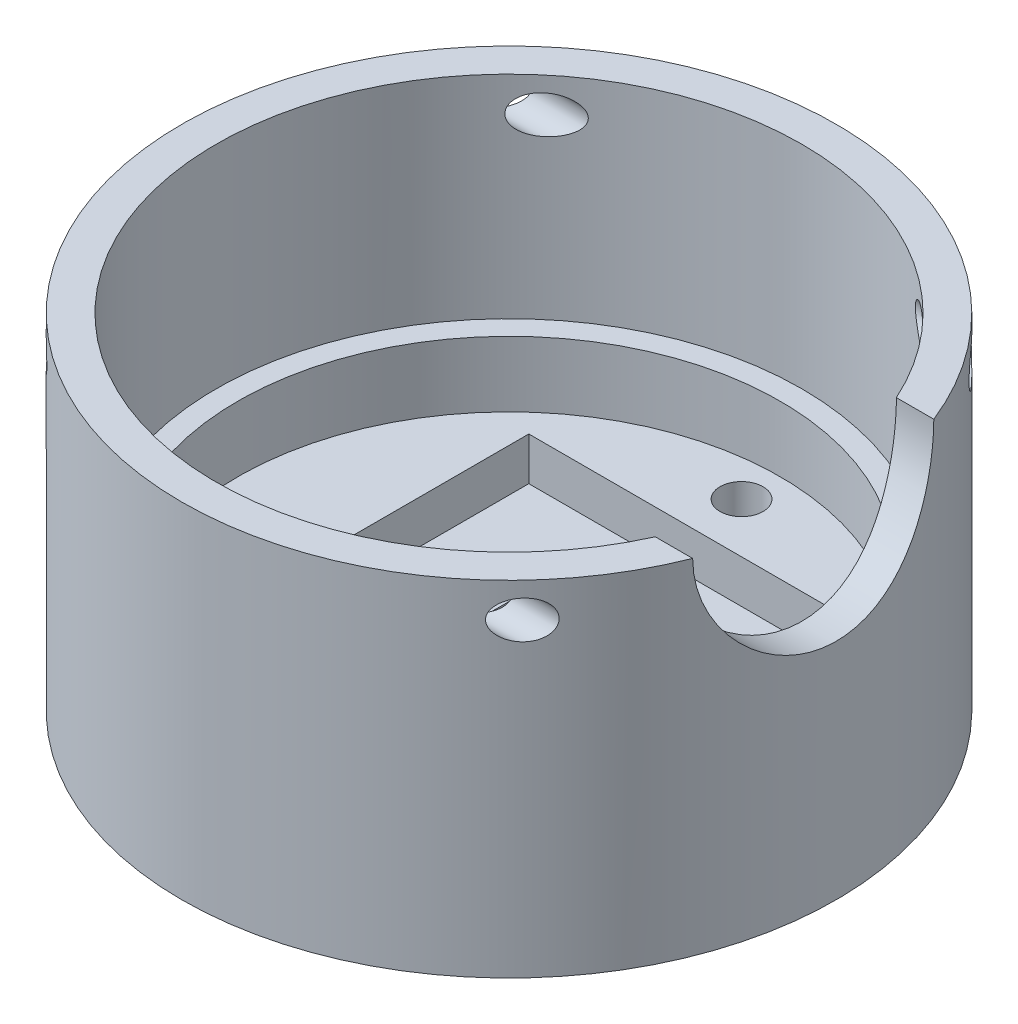
SolidWorks part; units mm, degrees
ref_plane "Front Plane" through (0, 0, 0) normal (0, 0, 1) x (1, 0, 0)
ref_plane "Top Plane" through (0, 0, 0) normal (0, 1, 0) x (1, 0, 0)
ref_plane "Right Plane" through (0, 0, 0) normal (1, 0, 0) x (0, 0, -1)
sketch "Sketch3" plane through (0, 0, 0) normal (0, 1, 0) x (1, 0, 0)
  circle A0 centre (0, 0) radius 19
  dimension "D1" = 38
extrude "Main Body" add sketch "Sketch3" against normal blind 20
sketch "Sketch5" plane through (0, -20, 0) normal (0, -1, 0) x (1, 0, 0)
  circle A0 centre (0, 0) radius 17
  circle A1 centre (0, 0) radius 19 construction
  dimension "D1" = 2
extrude "Cut for Headers" cut sketch "Sketch5" against normal through all from offset 7.7 offset against normal yes
ref_axis "Central Axis" through (0, 1, 0) along (0, -1, 0)
ref_axis "Horizontal Axis" through (-20.9, 0, 0) along (1, 0, 0)
ref_axis "Vertical Axis" through (0, 0, -20.9) along (0, 0, 1)
sketch "Sketch7" plane through (0, 0, 0) normal (1, 0, 0) x (0, 0, -1)
  circle A0 centre (0, 0) radius 7
  point P3 (0, -3.3432)
  dimension "D1" = 14
extrude "Cut for ADNS Wires" cut sketch "Sketch7" along normal up to next
sketch "Sketch8" plane through (0, -12.3, 0) normal (0, 1, 0) x (1, 0, 0)
  circle A0 centre (0, 0) radius 15.75
  dimension "D1" = 31.5
extrude "Cut for PCB" cut sketch "Sketch8" against normal blind 3.8
sketch "Sketch9" plane through (0, -16.1, 0) normal (0, 1, 0) x (1, 0, 0)
  line L0 (0, 15.75) -> (0, -15.75) construction
  line L1 (-15.75, 0) -> (15.75, 0) construction
  circle A1 centre (0, 0) radius 15.75 construction
  circle A2 centre (0, 13.5) radius 1.25
  circle A3 centre (0, -13.5) radius 1.25
  point P0 (0, 0)
  dimension "D1" = 2.5
  dimension "D2" = 27
extrude "Cut for Screw Holes" cut sketch "Sketch9" against normal blind 5
sketch "Sketch10" plane through (0, -16.1, 0) normal (0, 1, 0) x (1, 0, 0)
  line L1 (-9.45, -10.6) -> (9.45, -10.6)
  line L2 (-9.45, -10.6) -> (-9.45, 10.6)
  line L3 (-9.45, 10.6) -> (9.45, 10.6)
  line L4 (9.45, -10.6) -> (9.45, 10.6)
  line L5 (-9.45, -10.6) -> (9.45, 10.6) construction
  line L6 (-9.45, 10.6) -> (9.45, -10.6) construction
  point P0 (0, 0)
  dimension "D1" = 18.9
  dimension "D2" = 21.2
extrude "Cut for Lens" cut sketch "Sketch10" against normal blind 2.5
sketch "Sketch11" plane through (0, -18.6, 0) normal (0, 1, 0) x (1, 0, 0)
  line L1 (-4.1, -5.1) -> (4.1, -5.1)
  line L2 (-4.1, -5.1) -> (-4.1, 5.1)
  line L3 (-4.1, 5.1) -> (4.1, 5.1)
  line L4 (4.1, -5.1) -> (4.1, 5.1)
  line L5 (-4.1, -5.1) -> (4.1, 5.1) construction
  line L6 (-4.1, 5.1) -> (4.1, -5.1) construction
  point P0 (0, 0)
  dimension "D1" = 10.2
  dimension "D2" = 8.2
extrude "Cut for Pupil" cut sketch "Sketch11" against normal up to next
sketch "Sketch13" plane through (0, 0, 0) normal (1, 0, 0) x (0, 0, -1)
  line L0 (0, 1) -> (0, -21) construction
  line L1 (20.9, 0) -> (-20.9, 0) construction
  circle A0 centre (13, -2) radius 1.1
  circle A1 centre (-13, -2) radius 1.1
  point P0 (13, -2)
  point P7 (-13, -2)
  dimension "D3" = 2.2
  dimension "D4" = 13
  dimension "D5" = 2.2
  dimension "D1" = 13
  dimension "D2" = 2
extrude "Cuts for Body Screw Holes" cut sketch "Sketch13" against normal through all both and the other way through all
